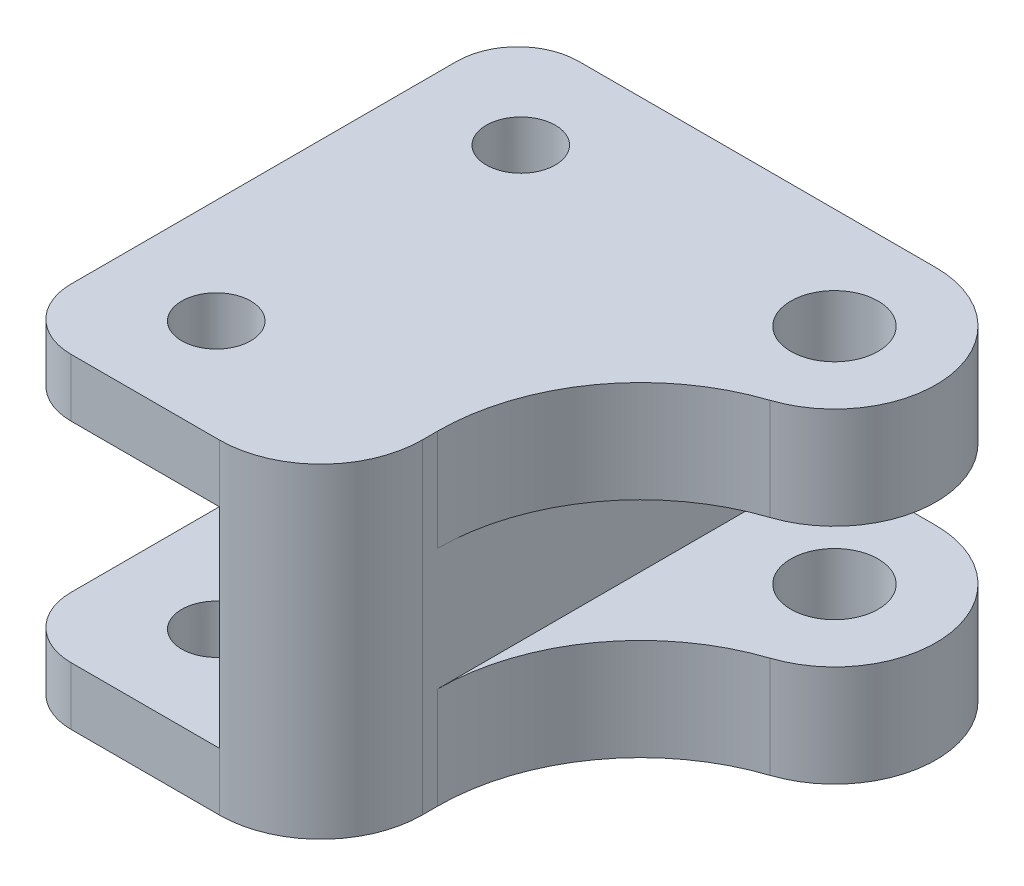
SolidWorks part; units mm, degrees
material "ﾎﾟﾘｴﾁﾚﾝｲﾐﾝ(PEI)"
ref_plane "正面" through (0, 0, 0) normal (0, 0, 1) x (1, 0, 0)
ref_plane "平面" through (0, 0, 0) normal (0, 1, 0) x (1, 0, 0)
ref_plane "右側面" through (0, 0, 0) normal (1, 0, 0) x (0, 0, -1)
sketch "ｽｹｯﾁ1" plane through (0, 0, 0) normal (0, 0, 1) x (1, 0, 0)
  line L0 (10.15, 0) -> (-5.15, 0)
  line L1 (5.15, 5.15) -> (-5.15, 5.15)
  line L2 (5.15, 5.15) -> (5.15, -5.15)
  line L3 (5.15, -5.15) -> (-5.15, -5.15)
  line L4 (-5.15, 5.15) -> (-5.15, -5.15)
  line L5 (5.15, 5.15) -> (-5.15, -5.15) construction
  line L6 (5.15, -5.15) -> (-5.15, 5.15) construction
  line L7 (-5.15, -8) -> (10.15, -8)
  line L8 (-5.15, -8) -> (-5.15, 8)
  line L9 (-5.15, 8) -> (10.15, 8)
  line L10 (10.15, -8) -> (10.15, 8)
  point P0 (0, 0)
  dimension "D1" = 10.3
  dimension "D2" = 10.3
  dimension "D3" = 0
  dimension "D4" = 16
  dimension "D5" = 5
  dimension "D6" = 0
extrude "ﾎﾞｽ - 押し出し1" add sketch "ｽｹｯﾁ1" along normal blind 25 contours L10 | L0 L10 L9 L8 L1 L2 | L7 L10 L0 L2 L3 L8 | L10 region at (9.9773, -4, 0) region at (7.65, 0.1727, 0)
sketch "ｽｹｯﾁ2" plane through (0, -8, 0) normal (0, -1, 0) x (1, 0, 0)
  line L0 (-5.15, 0) -> (10.15, 0) construction
  line L1 (-5.15, 25) -> (5.15, 25)
  line L2 (-5.15, 25) -> (-5.15, 0)
  line L3 (-5.15, 0) -> (5.15, 0)
  line L4 (5.15, 25) -> (5.15, 0)
  line L6 (0, 25) -> (0, 0) construction
  circle A0 centre (0, 20) radius 1.7
  circle A1 centre (0, 5) radius 1.7
  dimension "D2" = 3.4
  dimension "D3" = 3.4
  dimension "D4" = 5
  dimension "D5" = 5
  dimension "D1" = 10.3
extrude "ｶｯﾄ - 押し出し1" cut sketch "ｽｹｯﾁ2" against normal through all contours A0 | A1
sketch "ｽｹｯﾁ3" plane through (0, -8, 0) normal (0, -1, 0) x (1, 0, 0)
  line L0 (10.15, 25) -> (10.15, 0) construction
  line L1 (-5.15, 0) -> (10.15, 0) construction
  line L3 (15.45, 0) -> (10.15, 0)
  line L4 (15.45, 0) -> (15.45, 10) construction
  line L5 (15.45, 10) -> (10.15, 10)
  line L6 (10.15, 0) -> (10.15, 10) construction
  circle A0 centre (15.45, 5) radius 5
  circle A1 centre (15.45, 5) radius 2.15
  line M9 (10.15, 0) -> (10.15, 25)
  dimension "D1" = 10
  dimension "D2" = 4.3
  dimension "D3" = 10
  dimension "D4" = 5.3
extrude "ﾎﾞｽ - 押し出し2" add sketch "ｽｹｯﾁ3" against normal through all contours A0 L5 M9 | A0 L3 M9 | A0 A1 region at (12.8, -8, 0.1132) region at (10.5914, -8, 5)
sketch "ｽｹｯﾁ4" plane through (10.15, 0, 0) normal (1, 0, 0) x (0, 0, -1)
  line L1 (10, 3) -> (-10, 3)
  line L2 (10, 3) -> (10, -3)
  line L3 (10, -3) -> (-10, -3)
  line L4 (-10, 3) -> (-10, -3)
  line L5 (10, 3) -> (-10, -3) construction
  line L6 (10, -3) -> (-10, 3) construction
  point P0 (0, 0)
  dimension "D1" = 6
  dimension "D2" = 20
extrude "ｶｯﾄ - 押し出し2" cut sketch "ｽｹｯﾁ4" along normal through all
fillet "ﾌｨﾚｯﾄ1" radius 10 2 edges at (10.15, -5.5, 10) (10.15, 5.5, 10)
fillet "ﾌｨﾚｯﾄ2" radius 5 1 edges at (10.15, 0, 25)
fillet "ﾌｨﾚｯﾄ3" radius 3 4 edges at (-5.15, 6.575, 0) (-5.15, -6.575, 0) (-5.15, -6.575, 25) (-5.15, 6.575, 25)
